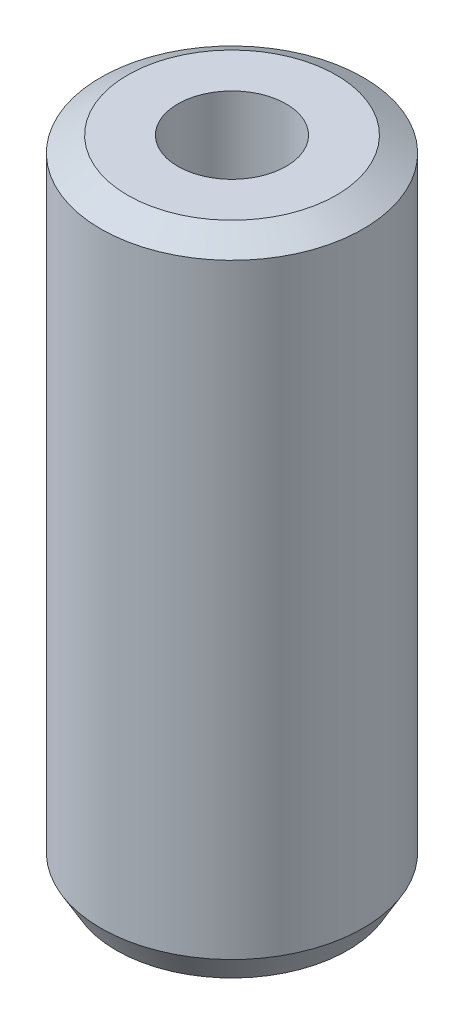
SolidWorks part; units mm, degrees
ref_plane "Front Plane" through (0, 0, 0) normal (0, 0, 1) x (1, 0, 0)
ref_plane "Top Plane" through (0, 0, 0) normal (0, 1, 0) x (1, 0, 0)
ref_plane "Right Plane" through (0, 0, 0) normal (1, 0, 0) x (0, 0, -1)
sketch "Sketch1" plane through (0, 0, 0) normal (0, 1, 0) x (1, 0, 0)
  circle A0 centre (0, 0) radius 47.5
  dimension "SHAFT_OD" = 95
extrude "Boss-Extrude1" add sketch "Sketch1" along normal blind 234.5245
sketch "Sketch2" plane through (0, 0, 0) normal (0, 1, 0) x (1, 0, 0)
  circle A0 centre (0, 0) radius 19.5971
  dimension "BORE_D" = 39.1942
extrude "Cut-Extrude1" cut sketch "Sketch2" along normal through all
chamfer "Chamfer1" distance 5.6452 angle 60 2 edges at (0, 234.5245, 47.5) (0, 0, 47.5) first distance on face at (0, 234.5245, 47.5) first distance on face at (0, 0, 19.5971)
